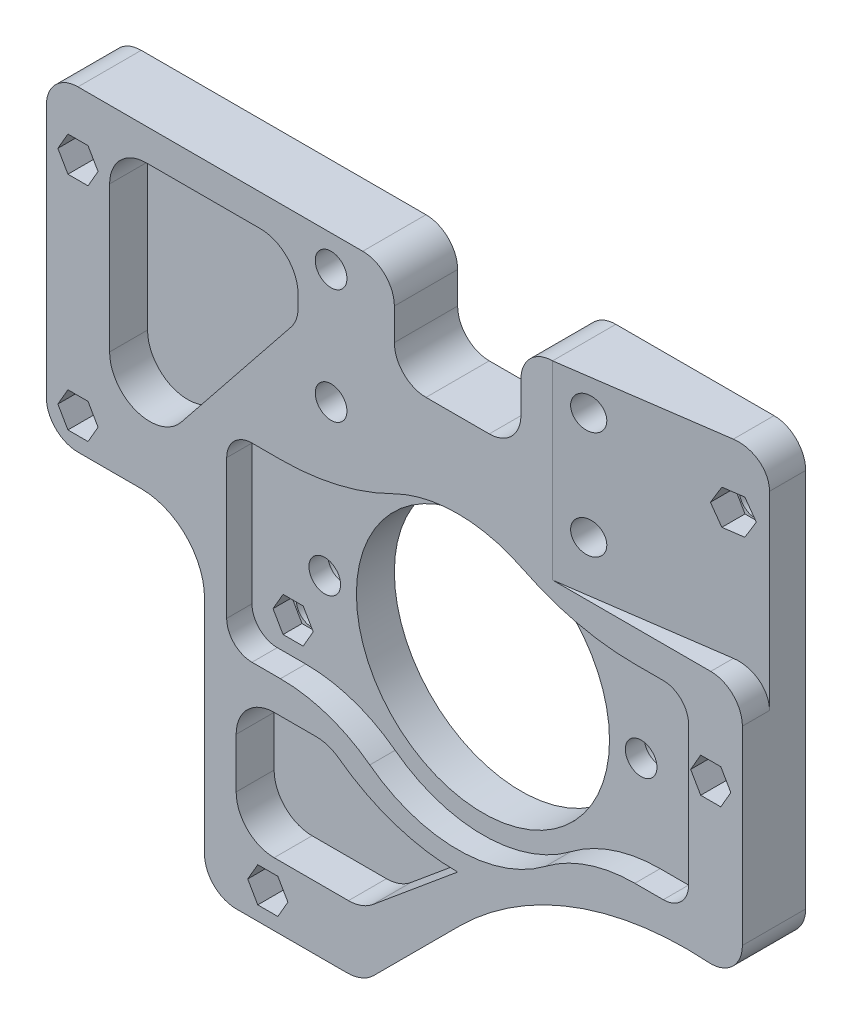
SolidWorks part; units mm, degrees
material "ABS"
ref_plane "Front Plane" through (0, 0, 0) normal (0, 0, 1) x (1, 0, 0)
ref_plane "Top Plane" through (0, 0, 0) normal (0, 1, 0) x (1, 0, 0)
ref_plane "Right Plane" through (0, 0, 0) normal (1, 0, 0) x (0, 0, -1)
sketch "Sketch1" plane through (0, 0, 0) normal (0, 0, 1) x (1, 0, 0)
  line L0 (0, 30) -> (-45, 30)
  line L1 (-50, 25) -> (-50, -15)
  line L2 (-45, -20) -> (-35, -20)
  line L3 (-25, -30) -> (-25, -65)
  line L4 (-20, -70) -> (-2.4853, -70)
  line L5 (1.7574, -68.2426) -> (15.2807, -54.7193)
  line L7 (60, -35.0122) -> (60, 25)
  line L8 (55, 30) -> (30, 30)
  line L9 (25, 25) -> (25, 20)
  line L10 (20, 15) -> (10, 15)
  line L11 (5, 20) -> (5, 25)
  arc A0 (-45, 30) -> (-50, 25) centre (-45, 25) ccw
  arc A1 (-35, -20) -> (-25, -30) centre (-35, -30) cw
  arc A2 (10, 15) -> (5, 20) centre (10, 20) cw
  arc A3 (25, 20) -> (20, 15) centre (20, 20) cw
  arc A4 (0, 30) -> (5, 25) centre (0, 25) cw
  arc A5 (30, 30) -> (25, 25) centre (30, 25) ccw
  arc A6 (60, 25) -> (55, 30) centre (55, 25) ccw
  arc A7 (-25, -65) -> (-20, -70) centre (-20, -65) ccw
  arc A8 (-2.4853, -70) -> (1.7574, -68.2426) centre (-2.4853, -64) ccw
  arc A9 (-50, -15) -> (-45, -20) centre (-45, -15) ccw
  arc A10 (54.6511, -40) -> (60, -35.0122) centre (55, -35.0122) ccw
  arc A11 (54.6511, -40) -> (15.2807, -54.7193) centre (51.1145, -90.5531) ccw
  point P22 (5, 30)
  dimension "D8" = 5
  dimension "D9" = 10
  dimension "D10" = 5
  dimension "D11" = 6
  dimension "D12" = 5
  dimension "D14" = 5
  dimension "D19" = 50.6766
  dimension "D1" = 55
  dimension "D2" = 50
  dimension "D3" = 20
  dimension "D4" = 35
  dimension "D5" = 50
  dimension "D6" = 15
  dimension "D7" = 135
  dimension "D13" = 70
  dimension "D15" = 17.5147
  dimension "D16" = 30
  dimension "D17" = 50
  dimension "D18" = 10
extrude "Figure Extrude" add sketch "Sketch1" along normal blind 10
sketch "Sketch2" plane through (0, 0, 0) normal (0, 0, 1) x (1, 0, 0)
  line L1 (15, 42.4516) -> (15, -63.1797) construction
  line L2 (20, 15) -> (10, 15) construction
  line L3 (55, 30) -> (30, 30) construction
  line L4 (60, -35.0122) -> (60, 25) construction
  line L5 (-50, 25) -> (-50, -15) construction
  line L6 (25, 25) -> (25, 20) construction
  line L7 (0, 30) -> (-45, 30) construction
  line L8 (5, 20) -> (5, 25) construction
  line L9 (-25, -30) -> (-25, -65) construction
  line L10 (-20, -70) -> (-2.4853, -70) construction
  circle A0 centre (15, -21.4) radius 20
  circle A1 centre (55, 20) radius 2.5
  circle A2 centre (55, -15) radius 2.5
  circle A3 centre (-45, 20) radius 2.5
  circle A4 centre (-45, -15) radius 2.5
  circle A5 centre (35, 25) radius 2.5
  circle A6 centre (35, 7.9862) radius 2.5
  circle A7 centre (-5, 25) radius 2.5
  circle A8 centre (-5, 6.8561) radius 2.5
  circle A9 centre (-15, -30) radius 2.5
  circle A10 centre (-15, -65) radius 2.5
  circle A11 centre (-10, -21.4) radius 2.5
  circle A12 centre (40, -21.4) radius 2.5
  dimension "D2" = 40
  dimension "D3" = 5
  dimension "D9" = 5
  dimension "D13" = 5
  dimension "D17" = 5
  dimension "D21" = 5
  dimension "D1" = 36.4
  dimension "D4" = 10
  dimension "D5" = 5
  dimension "D6" = 35
  dimension "D7" = 5
  dimension "D8" = 5
  dimension "D10" = 10
  dimension "D11" = 17.0138
  dimension "D12" = 5
  dimension "D14" = 10
  dimension "D15" = 18.1439
  dimension "D16" = 10
  dimension "D18" = 40
  dimension "D19" = 5
  dimension "D20" = 20
  dimension "D22" = 15
extrude "All 5mm Holes" cut sketch "Sketch2" along normal through all
sketch "Sketch3" plane through (0, 30, 0) normal (0, 1, 0) x (1, 0, 0)
  line L0 (30, -10) -> (60, -5.7143)
  line L1 (55, -10) -> (30, -10) construction
  line L2 (60, -10) -> (60, 0) construction
  line L3 (30, -10) -> (60, -10)
  line L4 (60, -10) -> (60, -5.7143)
  dimension "D1" = 8.13
  dimension "D2" = 30
extrude "Angled Plane Cut" cut sketch "Sketch3" against normal blind 30
fillet "Angled Plane Fillet" radius 5 1 edges at (60, 0, 7.8572)
sketch "Sketch4" plane through (0, 0, 10) normal (0, 0, 1) x (1, 0, 0)
  line L0 (-50, 25) -> (-50, -15) construction
  line L1 (-34.2175, 25) -> (-16.2175, 25)
  line L2 (-40, -3.7825) -> (-40, 19.2175)
  line L3 (0, 30) -> (-45, 30) construction
  line L4 (-11.3148, 13.9766) -> (-28.6947, -7.7482)
  line L5 (-45, -20) -> (-35, -20) construction
  line L6 (5, 20) -> (5, 25) construction
  line L7 (-10.2175, 19) -> (-10.2175, 17.1047)
  arc A0 (-40, 19.2175) -> (-34.2175, 25) centre (-34.2175, 19.2175) cw
  arc A1 (-40, -3.7825) -> (-28.6947, -7.7482) centre (-33.6518, -3.7825) ccw
  arc A2 (-16.2175, 25) -> (-10.2175, 19) centre (-16.2175, 19) cw
  arc A3 (-10.2175, 17.1047) -> (-11.3148, 13.9766) centre (-15.2248, 17.1047) cw
  dimension "D1" = 23
  dimension "D2" = 10
  dimension "D3" = 18
  dimension "D4" = 5
  dimension "D5" = 51.34
  dimension "D7" = 12.2518
  dimension "D8" = 16.3148
  dimension "D9" = 6
  dimension "D11" = 1.8953
extrude "Triangular cut" cut sketch "Sketch4" against normal blind 6
ref_plane "Plane1" through (0, 0, 10) normal (0, 0, 1) x (1, 0, 0)
sketch "Sketch5" plane through (0, 0, 10) normal (0, 0, 1) x (1, 0, 0)
  line L0 (-21.5, -9) -> (-21.5, -31)
  line L1 (51.5, -9) -> (51.5, -31)
  line L2 (47.5, -35) -> (43, -35)
  line L3 (47.5, -5) -> (43, -5)
  line L4 (-17.5, -5) -> (-13, -5)
  line L5 (-17.5, -35) -> (-13, -35)
  line L6 (-25, -30) -> (-25, -65) construction
  line L7 (-20, -70) -> (-2.4853, -70) construction
  line L8 (60, -35.0122) -> (60, -5) construction
  arc A0 (1.1213, -39.7407) -> (28.8787, -39.7407) centre (15, -21.4) ccw
  arc A1 (-21.5, -31) -> (-17.5, -35) centre (-17.5, -31) ccw
  arc A2 (-21.5, -9) -> (-17.5, -5) centre (-17.5, -9) cw
  arc A3 (51.5, -31) -> (47.5, -35) centre (47.5, -31) cw
  arc A4 (51.5, -9) -> (47.5, -5) centre (47.5, -9) ccw
  arc A5 (-13, -5) -> (4.7279, -0.8213) centre (-13, 34.6939) ccw
  arc A6 (-13, -35) -> (1.1213, -39.7407) centre (-13, -58.4021) cw
  arc A7 (43, -35) -> (28.8787, -39.7407) centre (43, -58.4021) ccw
  arc A8 (43, -5) -> (25.2721, -0.8213) centre (43, 34.6939) cw
  arc A9 (25.2721, -0.8213) -> (4.7279, -0.8213) centre (15, -21.4) ccw
  dimension "D1" = 46
  dimension "D2" = 4
  dimension "D5" = 4
  dimension "D3" = 3.5
  dimension "D4" = 35
  dimension "D6" = 8.5
  dimension "D7" = 30
  dimension "D8" = 4.5
  dimension "D9" = 4.5
extrude "Middle Circular Cut" cut sketch "Sketch5" against normal blind 4
sketch "Sketch6" plane through (0, 0, 10) normal (0, 0, 1) x (1, 0, 0)
  line L0 (-20, -54) -> (-20, -46.1088)
  line L1 (-14, -40.1088) -> (-7.3445, -40.1088)
  line L2 (-14, -60) -> (-2.2487, -60)
  line L3 (1.5871, -58.6137) -> (15, -47.4623)
  line L4 (-25, -30) -> (-25, -65) construction
  line L5 (-20, -70) -> (-2.4853, -70) construction
  line L6 (15, 30.8608) -> (15, -114.106) construction
  arc A0 (-20, -54) -> (-14, -60) centre (-14, -54) ccw
  arc A1 (-20, -46.1088) -> (-14, -40.1088) centre (-14, -46.1088) cw
  arc A2 (15, -47.4623) -> (-3.7812, -41.2815) centre (15, -15.8373) cw
  arc A7 (-2.2487, -60) -> (1.5871, -58.6137) centre (-2.2487, -54) ccw
  arc A8 (-7.3445, -40.1088) -> (-3.7812, -41.2815) centre (-7.3445, -46.1088) cw
  dimension "D3" = 6
  dimension "D5" = 31.6249
  dimension "D4" = 6
  dimension "D1" = 5
  dimension "D2" = 10
  dimension "D6" = 19.8912
  dimension "D7" = 140.26
  dimension "D8" = 6.6555
extrude "Cut-Extrude12" cut sketch "Sketch6" against normal blind 6
sketch "Sketch7" plane through (0, 0, 0) normal (0, 0, -1) x (-1, 0, 0)
  circle A0 centre (-40, -21.4) radius 3.75
  circle A1 centre (10, -21.4) radius 3.75
  dimension "D1" = 7.5
extrude "Cut-Extrude13" cut sketch "Sketch7" against normal blind 3
sketch "Sketch8" plane through (0, 0, 0) normal (0, 0, -1) x (-1, 0, 0)
  line L0 (0, 30) -> (45, 30) construction
  line L1 (-33.4123, 27.75) -> (-36.5877, 27.75)
  line L2 (-36.5877, 27.75) -> (-38.1754, 25)
  line L3 (-38.1754, 25) -> (-36.5877, 22.25)
  line L4 (-36.5877, 22.25) -> (-33.4123, 22.25)
  line L5 (-33.4123, 22.25) -> (-31.8246, 25)
  line L6 (-31.8246, 25) -> (-33.4123, 27.75)
  line L7 (-33.4123, 10.7362) -> (-36.5877, 10.7362)
  line L8 (-36.5877, 10.7362) -> (-38.1754, 7.9862)
  line L9 (-38.1754, 7.9862) -> (-36.5877, 5.2362)
  line L10 (-36.5877, 5.2362) -> (-33.4123, 5.2362)
  line L11 (-33.4123, 5.2362) -> (-31.8246, 7.9862)
  line L12 (-31.8246, 7.9862) -> (-33.4123, 10.7362)
  line L13 (3.4123, 9.6061) -> (1.8246, 6.8561)
  line L14 (1.8246, 6.8561) -> (3.4123, 4.1061)
  line L15 (3.4123, 4.1061) -> (6.5877, 4.1061)
  line L16 (6.5877, 4.1061) -> (8.1754, 6.8561)
  line L17 (8.1754, 6.8561) -> (6.5877, 9.6061)
  line L18 (6.5877, 9.6061) -> (3.4123, 9.6061)
  line L19 (3.4123, 27.75) -> (1.8246, 25)
  line L20 (1.8246, 25) -> (3.4123, 22.25)
  line L21 (3.4123, 22.25) -> (6.5877, 22.25)
  line L22 (6.5877, 22.25) -> (8.1754, 25)
  line L23 (8.1754, 25) -> (6.5877, 27.75)
  line L24 (6.5877, 27.75) -> (3.4123, 27.75)
  line L25 (-55, 30) -> (-30, 30) construction
  circle A0 centre (-35, 25) radius 2.75 construction
  circle A1 centre (-35, 7.9862) radius 2.75 construction
  circle A2 centre (5, 6.8561) radius 2.75 construction
  circle A3 centre (5, 25) radius 2.75 construction
  dimension "D1" = 3.1754
extrude "Cut-Extrude14" cut sketch "Sketch8" against normal blind 5
sketch "Sketch9" plane through (0, 0, 10) normal (0, 0, 1) x (1, 0, 0)
  line L0 (0, 30) -> (-45, 30) construction
  line L1 (-46.5877, 22.75) -> (-48.1754, 20)
  line L2 (-48.1754, 20) -> (-46.5877, 17.25)
  line L3 (-46.5877, 17.25) -> (-43.4123, 17.25)
  line L4 (-43.4123, 17.25) -> (-41.8246, 20)
  line L5 (-41.8246, 20) -> (-43.4123, 22.75)
  line L6 (-43.4123, 22.75) -> (-46.5877, 22.75)
  line L7 (-43.4123, -12.25) -> (-46.5877, -12.25)
  line L8 (-46.5877, -12.25) -> (-48.1754, -15)
  line L9 (-48.1754, -15) -> (-46.5877, -17.75)
  line L10 (-46.5877, -17.75) -> (-43.4123, -17.75)
  line L11 (-43.4123, -17.75) -> (-41.8246, -15)
  line L12 (-41.8246, -15) -> (-43.4123, -12.25)
  line L13 (-13.4123, -62.25) -> (-16.5877, -62.25)
  line L14 (-16.5877, -62.25) -> (-18.1754, -65)
  line L15 (-18.1754, -65) -> (-16.5877, -67.75)
  line L16 (-16.5877, -67.75) -> (-13.4123, -67.75)
  line L17 (-13.4123, -67.75) -> (-11.8246, -65)
  line L18 (-11.8246, -65) -> (-13.4123, -62.25)
  line L19 (-13.4123, -27.25) -> (-16.5877, -27.25)
  line L20 (-16.5877, -27.25) -> (-18.1754, -30)
  line L21 (-18.1754, -30) -> (-16.5877, -32.75)
  line L22 (-16.5877, -32.75) -> (-13.4123, -32.75)
  line L23 (-13.4123, -32.75) -> (-11.8246, -30)
  line L24 (-11.8246, -30) -> (-13.4123, -27.25)
  line L25 (56.5877, -12.25) -> (53.4123, -12.25)
  line L26 (53.4123, -12.25) -> (51.8246, -15)
  line L27 (51.8246, -15) -> (53.4123, -17.75)
  line L28 (53.4123, -17.75) -> (56.5877, -17.75)
  line L29 (56.5877, -17.75) -> (58.1754, -15)
  line L30 (58.1754, -15) -> (56.5877, -12.25)
  line L31 (56.5877, 22.75) -> (53.4123, 22.75)
  line L32 (53.4123, 22.75) -> (51.8246, 20)
  line L33 (51.8246, 20) -> (53.4123, 17.25)
  line L34 (53.4123, 17.25) -> (56.5877, 17.25)
  line L35 (56.5877, 17.25) -> (58.1754, 20)
  line L36 (58.1754, 20) -> (56.5877, 22.75)
  circle A0 centre (-45, 20) radius 2.75 construction
  circle A1 centre (-45, -15) radius 2.75 construction
  circle A2 centre (-15, -65) radius 2.75 construction
  circle A3 centre (-15, -30) radius 2.75 construction
  circle A4 centre (55, -15) radius 2.75 construction
  circle A5 centre (55, 20) radius 2.75 construction
  dimension "D1" = 3.1754
extrude "Cut-Extrude15" cut sketch "Sketch9" against normal blind 7 contours L5 L6 L1 L2 L3 L4 | L11 L12 L7 L8 L9 L10 | L17 L18 L13 L14 L15 L16 | L29 L30 L25 L26 L27 L28 | L35 L36 L31 L32 L33 L34 region at (-45, 20, 10) region at (-45, -15, 10) region at (-15, -65, 10) region at (55, -15, 10) region at (55, 20, 10)
extrude "Cut-Extrude17" cut sketch "Sketch9<4>" against normal blind 7 contours L23 L24 L19 L20 L21 L22 region at (-15, -30, 10)
sketch "Sketch9<4>" plane through (0, 0, 10) normal (0, 0, 1) x (1, 0, 0) same geometry as "Sketch9"
